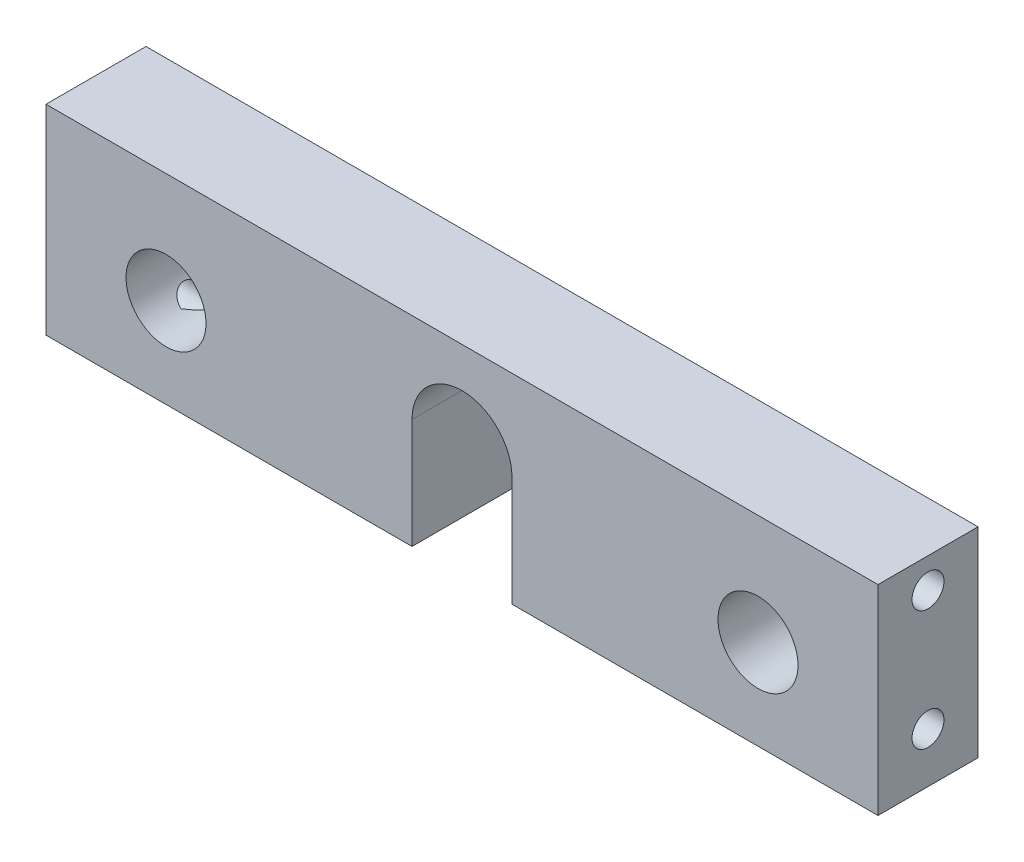
SolidWorks part; units mm, degrees
ref_plane "Front Plane" through (0, 0, 0) normal (0, 0, 1) x (1, 0, 0)
ref_plane "Top Plane" through (0, 0, 0) normal (0, 1, 0) x (1, 0, 0)
ref_plane "Right Plane" through (0, 0, 0) normal (1, 0, 0) x (0, 0, -1)
sketch "Sketch1" plane through (0, 0, 0) normal (1, 0, 0) x (0, 0, -1)
  line L0 (-2.5, 0) -> (2.5, 0)
  line L1 (-2.5, 0) -> (-2.5, 10)
  line L2 (-2.5, 10) -> (2.5, 10)
  line L3 (2.5, 10) -> (2.5, 0)
  dimension "D1" = 5
  dimension "D2" = 10
extrude "Boss-Extrude1" add sketch "Sketch1" along normal blind 41.6
hole_wizard "Tap Drill for M2x0.4 Tap1" positions "Sketch3" profile "Sketch2" hole size "M2x0.4" standard "ANSI Metric"
sketch "Sketch3" plane through (41.6, 0, 0) normal (1, 0, 0) x (0, 0, -1)
  line L0 (-2.5, 0) -> (2.5, 0) construction
  point P0 (0, 8.5)
  point P2 (0, 2.5)
  dimension "D1" = 6
  dimension "D2" = 2.5
sketch "Sketch2" plane through (41.6, 8.5, 0) normal (0, 1, 0) x (0, 0, -1)
  line L0 (0, 0) -> (0, 5.4807)
  line L1 (0, 5.4807) -> (0.8, 5)
  line L2 (0.8, 5) -> (0.8, 0)
  line L5 (0.8, 0) -> (0, 0)
  line L10 (0, 5.4807) -> (-0.8, 5) construction
  line L11 (0, -6.35) -> (0, 107.95) construction
  dimension "Hole Dia." = 1.6
  dimension "Hole Depth" = 5
  dimension "Drill Angle" = 118
hole_wizard "Tap Drill for M2x0.4 Tap2" positions "Sketch5" profile "Sketch4" hole size "M2x0.4" standard "ANSI Metric"
sketch "Sketch5" plane through (0, 0, 0) normal (-1, 0, 0) x (0, 0, 1)
  point P0 (0, 8.5)
  point P2 (0, 2.5)
  dimension "D1" = 2.5
  dimension "D2" = 6
sketch "Sketch4" plane through (0, 8.5, 0) normal (0, 1, 0) x (0, 0, 1)
  line L0 (0, 0) -> (0, 5.4807)
  line L1 (0, 5.4807) -> (0.8, 5)
  line L2 (0.8, 5) -> (0.8, 0)
  line L5 (0.8, 0) -> (0, 0)
  line L10 (0, 5.4807) -> (-0.8, 5) construction
  line L11 (0, -6.35) -> (0, 107.95) construction
  dimension "Hole Dia." = 1.6
  dimension "Hole Depth" = 5
  dimension "Drill Angle" = 118
sketch "Sketch8" plane through (0, 0, 2.5) normal (0, 0, 1) x (1, 0, 0)
  line L0 (18.3, 0) -> (18.3, 5.5)
  line L2 (23.3, 5.5) -> (23.3, 0)
  line L3 (23.3, 0) -> (18.3, 0)
  line L5 (0, 10) -> (0, 0) construction
  line L6 (41.6, 10) -> (0, 10) construction
  line L7 (41.6, 10) -> (41.6, 0) construction
  line L8 (0, 10) -> (0, 0) construction
  line L9 (41.6, 0) -> (0, 0) construction
  circle A0 centre (6, 4.5) radius 2
  circle A1 centre (35.6, 4.5) radius 2
  arc A2 (18.3, 5.5) -> (23.3, 5.5) centre (20.8, 5.5) cw
  dimension "D1" = 4
  dimension "D2" = 2.5
  dimension "D3" = 20.8
  dimension "D4" = 6
  dimension "D5" = 5.5
  dimension "D6" = 6
  dimension "D7" = 4.5
extrude "Cut-Extrude1" cut sketch "Sketch8" against normal up to next
